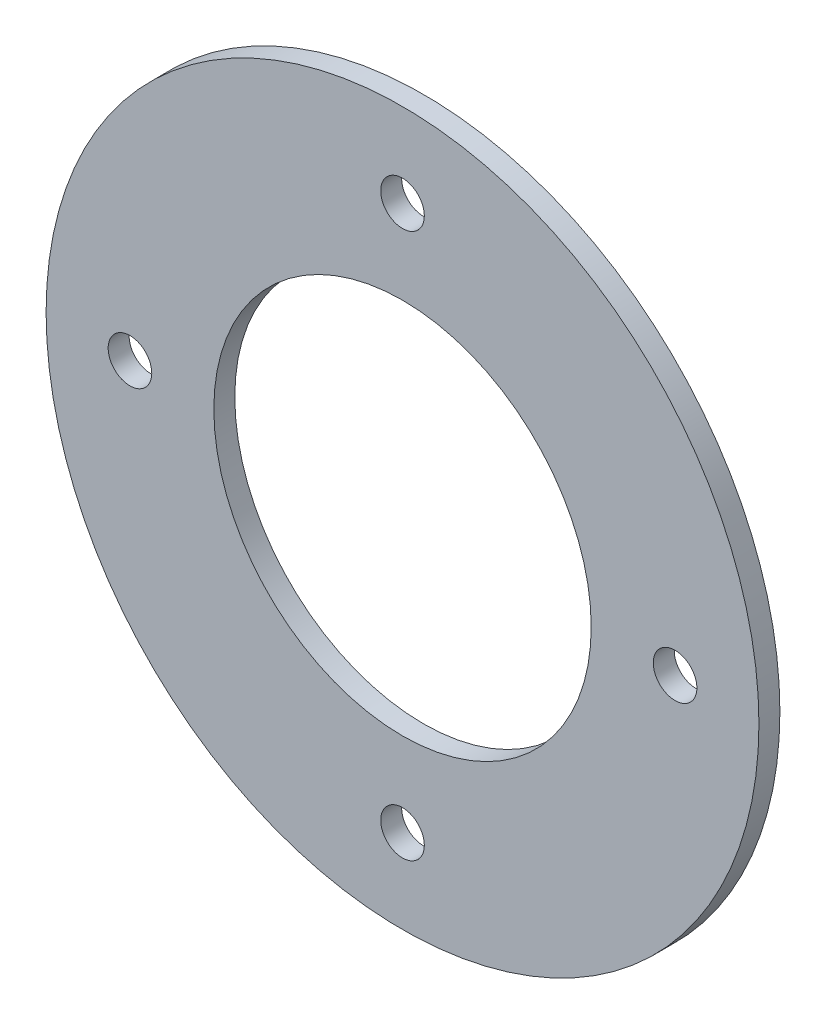
SolidWorks part; units mm, degrees
ref_plane "Front Plane" through (0, 0, 0) normal (0, 0, 1) x (1, 0, 0)
ref_plane "Top Plane" through (0, 0, 0) normal (0, 1, 0) x (1, 0, 0)
ref_plane "Right Plane" through (0, 0, 0) normal (1, 0, 0) x (0, 0, -1)
sketch "Sketch1" plane through (0, 0, 0) normal (0, 0, 1) x (1, 0, 0)
  circle A0 centre (0, 0) radius 14.2875
  circle A1 centre (0, 0) radius 26.9875
  dimension "D1" = 28.575
  dimension "D2" = 12.7
base flange "Base-Flange1" sketch "Sketch1" thickness 1.5875 reverse thickness direction no parameters "D1"=0.7366
sketch "Sketch6" plane through (0, 0, 0) normal (0, 0, 1) x (1, 0, 0)
  circle A0 centre (0, 20.6375) radius 1.651
  circle A1 centre (20.6375, 0) radius 1.651
  circle A2 centre (0, -20.6375) radius 1.651
  circle A3 centre (-20.6375, 0) radius 1.651
  circle A4 centre (0, 0) radius 20.6375 construction
  circle A5 centre (0, 0) radius 26.9875 construction
  dimension "D1" = 3.302
  dimension "D2" = 6.35
extrude "Cut-Extrude1" cut sketch "Sketch6" against normal through all normal cut yes
sketch "Bend-Lines1" [suppressed] plane through (0, 0, 0) normal (0, 1, 0) x (1, 0, 0)
sketch "Bounding-Box1" [suppressed] plane through (0, 0, 0) normal (0, 1, 0) x (1, 0, 0)
sheet metal parameters "Sheet-Metal1" thickness 1.5875 parameters "D1"=0.7366
flat pattern "Flat-Pattern1" [suppressed]
sketch "Bend-Lines2" plane through (0, 0, 0) normal (0, 1, 0) x (1, 0, 0)
sketch3d "Bounding-Box2" [suppressed]
  line L0 (26.9292, -27.0456, 0) -> (-27.0456, -26.9293, 0) construction
  line L1 (27.0456, 26.9292, 0) -> (-26.9292, 27.0455, 0) construction
  line L2 (26.9292, -27.0456, 0) -> (27.0456, 26.9292, 0) construction
  line L3 (-27.0456, -26.9293, 0) -> (-26.9292, 27.0455, 0) construction
sheet metal parameters "Sheet-Metal2" thickness 1.5875 parameters "D1"=0.7366
flat pattern "Flat-Pattern1"
sketch "Bend-Lines2" plane through (0, 0, 0) normal (0, 1, 0) x (1, 0, 0)
sketch3d "Bounding-Box2" [suppressed]
  line L0 (-26.9292, -27.0456, 0) -> (27.0456, -26.9293, 0) construction
  line L1 (-27.0456, 26.9292, 0) -> (26.9292, 27.0455, 0) construction
  line L2 (-26.9292, -27.0456, 0) -> (-27.0456, 26.9292, 0) construction
  line L3 (27.0456, -26.9293, 0) -> (26.9292, 27.0455, 0) construction
